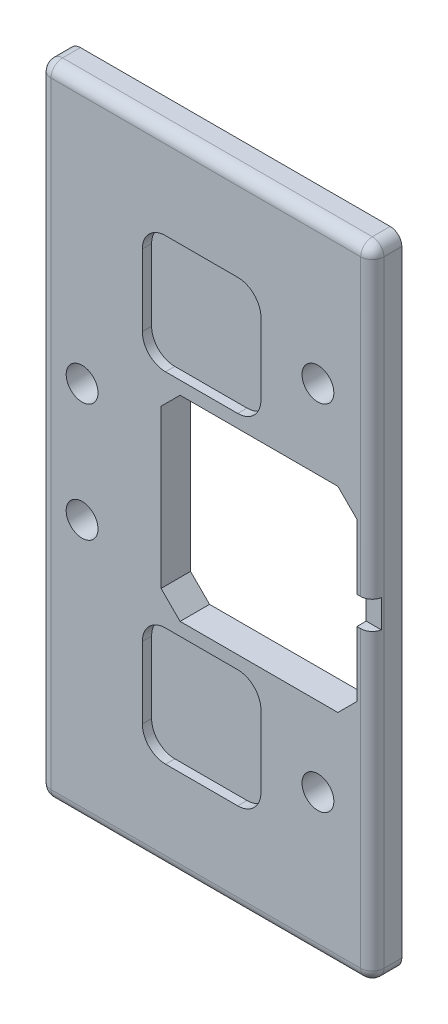
SolidWorks part; units mm, degrees
ref_plane "Front Plane" through (0, 0, 0) normal (0, 0, 1) x (1, 0, 0)
ref_plane "Top Plane" through (0, 0, 0) normal (0, 1, 0) x (1, 0, 0)
ref_plane "Right Plane" through (0, 0, 0) normal (1, 0, 0) x (0, 0, -1)
sketch "Sketch1" plane through (0, 0, 0) normal (0, 0, 1) x (1, 0, 0)
  line L0 (68.0566, 68.87) -> (126.0194, 68.87)
  line L22 (62.2146, 68.87) -> (68.0566, 68.87)
  line L28 (62.2146, -68.87) -> (126.0194, -68.87)
  line L31 (126.0194, -68.87) -> (126.0194, 68.87)
  line L38 (62.2146, 68.87) -> (54.2999, 68.87)
  line L40 (62.2146, -68.87) -> (54.2999, -68.87)
  line L41 (54.2999, 68.87) -> (54.2999, -68.87)
extrude "Boss-Extrude3" add sketch "Sketch1" along normal blind 6.35 contours L22 region at (90.1597, 0, 0)
ref_plane "Plane1" through (0, 0, 0) normal (0, -1, 0) x (-1, 0, 0)
sketch "Sketch6" plane through (0, 0, 0) normal (0, 0, -1) x (-1, 0, 0)
  circle A16 centre (-63.5, 12.7) radius 3.429
  circle A17 centre (-114.3, 38.1) radius 3.429
  circle A18 centre (-114.3, -38.1) radius 3.429
  circle A19 centre (-63.5, -12.7) radius 3.429
  dimension "D1" = 6.858
extrude "Cut-Extrude5" cut sketch "Sketch6" against normal up to surface (6.35 mm away) up to face at (90.1597, 0, 6.35)
fillet "Fillet2" radius 2.5 8 edges at (54.2999, 68.87, 3.175) (54.2999, -68.87, 3.175) (126.0194, -68.87, 3.175) (126.0194, 68.87, 3.175) (90.1597, 68.87, 6.35) (90.1597, -68.87, 6.35) (54.2999, 0, 6.35) (126.0194, 0, 6.35)
sketch "Sketch7" plane through (0, 0, 6.35) normal (0, 0, 1) x (1, 0, 0)
  line L0 (90.1597, -66.37) -> (90.1597, 66.37) construction
  line L3 (56.7999, -66.37) -> (123.5194, -66.37) construction
  line L5 (123.5194, 66.37) -> (56.7999, 66.37) construction
  line L6 (56.7999, 0) -> (123.5194, 0) construction
  line L7 (56.7999, 66.37) -> (56.7999, -66.37) construction
  line L8 (123.5194, -66.37) -> (123.5194, 66.37) construction
  circle A0 centre (90.1597, 0) radius 3.43
  dimension "D1" = 6.86
extrude "Cut-Extrude6" cut sketch "Sketch7" against normal through all
sketch "Sketch10" plane through (0, 0, 6.35) normal (0, 0, 1) x (1, 0, 0)
  line L0 (80.5121, 0) -> (56.7999, 0) construction
  line L14 (80.5121, 21.0947) -> (122.7015, 21.0947)
  line L15 (80.5121, 21.0947) -> (80.5121, -21.0947)
  line L16 (80.5121, -21.0947) -> (122.7015, -21.0947)
  line L17 (122.7015, 21.0947) -> (122.7015, -21.0947)
  line L18 (56.7999, 66.37) -> (56.7999, -66.37) construction
  dimension "D1" = 23.7122
extrude "Cut-Extrude8" cut sketch "Sketch10" against normal through all
sketch "Sketch11" plane through (0, 0, 6.35) normal (0, 0, 1) x (1, 0, 0)
  line L0 (123.5194, -66.37) -> (123.5194, 66.37) construction
  line L1 (123.5194, -3) -> (122.7015, -3)
  line L3 (123.5194, 3) -> (122.7015, 3)
  line L4 (122.7015, -3) -> (122.7015, 3)
  line L5 (122.7015, -21.0947) -> (122.7015, 21.0947) construction
  line L6 (123.1104, 3) -> (123.1104, 66.37) construction
  line L7 (123.5194, -3) -> (127.3985, -3)
  line L9 (123.5194, 3) -> (127.3985, 3)
  line L10 (127.3985, -3) -> (127.3985, 3)
  line L11 (123.5194, 66.37) -> (56.7999, 66.37) construction
  line L12 (123.1104, -3) -> (123.1104, -66.37) construction
  line L13 (56.7999, -66.37) -> (123.5194, -66.37) construction
  dimension "D1" = 6
extrude "Cut-Extrude9" cut sketch "Sketch11" against normal blind 2
sketch "Sketch12" plane through (0, 0, 6.35) normal (0, 0, 1) x (1, 0, 0)
  line L0 (76.4742, -44.3) -> (76.4742, -50.9707) construction
  line L1 (81.4742, -49.3) -> (76.4742, -49.3) construction
  line L2 (96.8742, -23.9) -> (102.0243, -23.9) construction
  line L3 (102.0243, -23.9) -> (101.8742, -28.9) construction
  line L5 (76.4742, -49.3) -> (102.0243, -49.3)
  line L6 (76.4742, -49.3) -> (76.4742, -23.9)
  line L7 (76.4742, -23.9) -> (102.0243, -23.9)
  line L8 (102.0243, -49.3) -> (102.0243, -23.9)
extrude "Cut-Extrude10" cut sketch "Sketch12" against normal blind 2
fillet "Fillet3" radius 5 4 edges at (102.0243, -23.9, 5.35) (76.4742, -23.9, 5.35) (76.4742, -49.3, 5.35) (102.0243, -49.3, 5.35)
mirror "Mirror1" about plane through (0, 0, 0) normal (0, -1, 0) of "Fillet3", "Cut-Extrude10"
chamfer "Chamfer1" distance 4.1 angle 45 4 edges at (80.5121, -21.0947, 3.175) (80.5121, 21.0947, 3.175) (122.7015, 21.0947, 3.175) (122.7015, -21.0947, 3.175)
